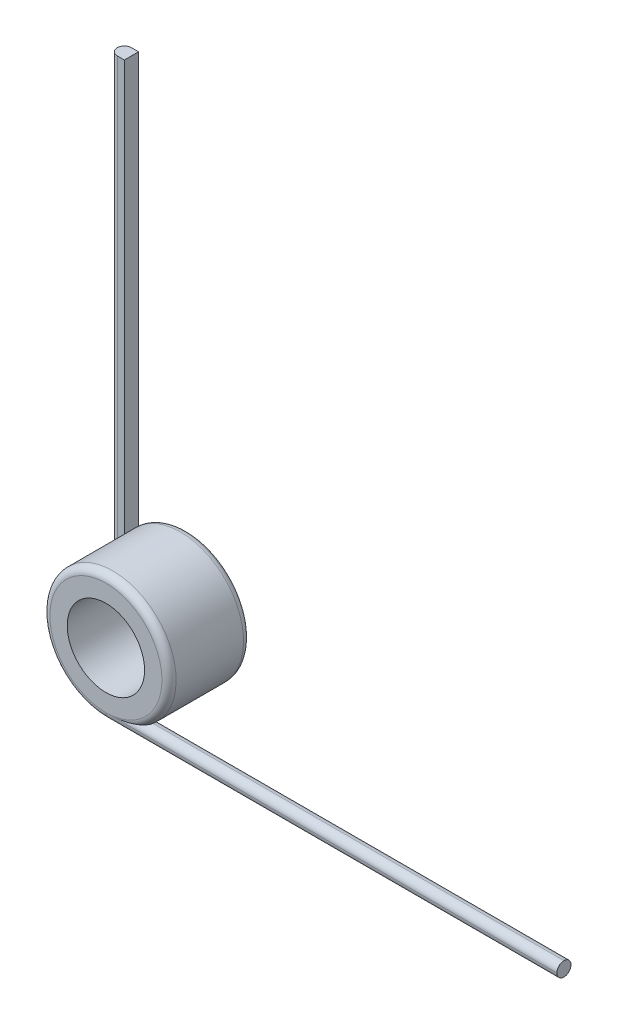
SolidWorks part; units mm, degrees
ref_plane "Front Plane" through (0, 0, 0) normal (0, 0, 1) x (1, 0, 0)
ref_plane "Top Plane" through (0, 0, 0) normal (0, 1, 0) x (1, 0, 0)
ref_plane "Right Plane" through (0, 0, 0) normal (1, 0, 0) x (0, 0, -1)
sketch "Sketch1" plane through (0, 0, 0) normal (0, 0, 1) x (1, 0, 0)
  circle A0 centre (0, 0) radius 7.112
  circle A1 centre (0, 0) radius 4.3561
  dimension "D1" = 14.224
  dimension "D2" = 8.7122
extrude "Boss-Extrude1" add sketch "Sketch1" along normal blind 9.1948
sketch "Sketch2" plane through (0, 0, 9.1948) normal (0, 0, 1) x (1, 0, 0)
  line L0 (-7.112, 0) -> (-7.112, 50.8)
  line L1 (-7.112, 50.8) -> (-5.5118, 50.8)
  line L2 (-5.5118, 50.8) -> (-5.5118, 4.4945)
  line L3 (0, 0) -> (0, -14.6657) construction
  circle A0 centre (0, 0) radius 7.112 construction
  arc A1 (-5.5118, 4.4945) -> (-7.112, 0) centre (0, 0) ccw
  dimension "D1" = 50.8
  dimension "D2" = 1.6002
  dimension "D3" = 180
extrude "Boss-Extrude2" add sketch "Sketch2" along normal blind 1.6002 from surface starting at face at (7.112, 0, 0)
fillet "Fillet1" radius 0.8001 3 edges at (-7.112, 25.4, 1.6002) (-7.112, 25.4, 0) (6.7, -2.3854, 0)
sketch "Sketch4" plane through (0, 0, 0) normal (0, 0, -1) x (-1, 0, 0)
  line L0 (0, -7.112) -> (-50.8, -7.112)
  line L1 (-50.8, -7.112) -> (-50.8, -5.5118)
  line L2 (-50.8, -5.5118) -> (-4.4945, -5.5118)
  circle A0 centre (0, 0) radius 7.112 construction
  arc A1 (-4.4945, -5.5118) -> (0, -7.112) centre (0, 0) ccw
  dimension "D1" = 1.6002
  dimension "D2" = 50.8
extrude "Boss-Extrude4" add sketch "Sketch4" along normal blind 1.6002 from surface starting at face at (7.112, 0, 9.1948)
fillet "Fillet2" radius 0.8001 5 edges at (25.4, -7.112, 7.5946) (27.6473, -5.5118, 7.5946) (25.4, -7.112, 9.1948) (27.6473, -5.5118, 9.1948) (-2.3854, 6.7, 9.1948)
equation "\"diam\"= .063"
equation "\"shaft\"= .343"
equation "\"od\"= .56in"
equation "\"length\"= .362"
equation "\"D1@Sketch1\"=\"od\""
equation "\"D2@Sketch1\"=\"shaft\""
equation "\"coils\"= 8"
equation "\"D1@Boss-Extrude1\"=\"length\""
equation "\"D1@Boss-Extrude2\"=\"diam\""
equation "\"D2@Sketch2\"=\"diam\""
equation "\"arm\"= 2"
equation "\"D1@Sketch2\"=\"arm\""
equation "\"D2@Sketch4\"=\"arm\""
equation "\"D1@Sketch4\"=\"diam\""
equation "\"D1@Boss-Extrude4\"=\"diam\""
equation "\"D1@Fillet2\"=\"diam\"/2"
equation "\"D1@Fillet1\"=\"diam\"/2"
